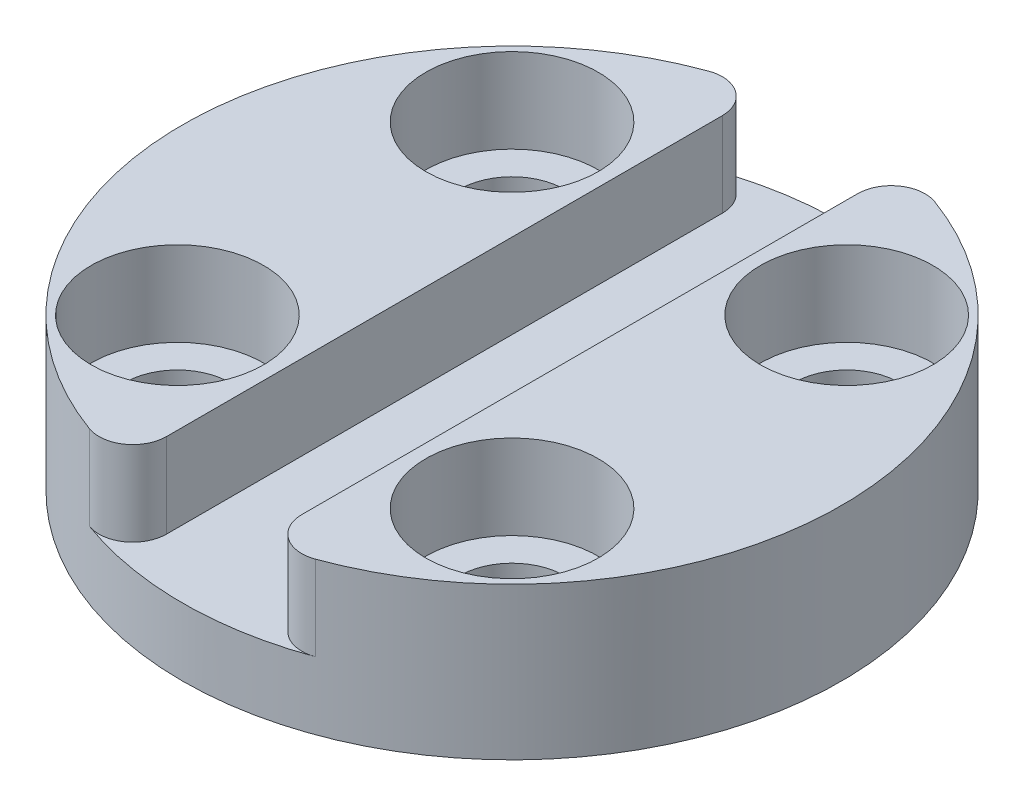
SolidWorks part; units mm, degrees
material "ABS"
ref_plane "前视基准面" through (0, 0, 0) normal (0, 0, 1) x (1, 0, 0)
ref_plane "上视基准面" through (0, 0, 0) normal (0, 1, 0) x (1, 0, 0)
ref_plane "右视基准面" through (0, 0, 0) normal (1, 0, 0) x (0, 0, -1)
sketch "草图1" plane through (0, 0, 0) normal (0, 1, 0) x (1, 0, 0)
  line L0 (0, 0) -> (8.1353, 8.1353) construction
  line L1 (0, 0) -> (0, 3.9878) construction
  circle A0 centre (0, 0) radius 9.75
  circle A1 centre (4.9497, 4.9497) radius 1.55
  circle A2 centre (4.9497, -4.9497) radius 1.55
  circle A3 centre (-4.9497, -4.9497) radius 1.55
  circle A4 centre (-4.9497, 4.9497) radius 1.55
  point P18 (0, 0)
  dimension "D1" = 19.5
  dimension "D2" = 3.1
  dimension "D3" = 7
  dimension "D4" = 45
  dimension "D5" = 4
extrude "凸台-拉伸1" add sketch "草图1" along normal blind 2
sketch "草图2" plane through (0, 2, 0) normal (0, 1, 0) x (1, 0, 0)
  line L0 (-2, 8.2196) -> (-2, -8.2196)
  line L1 (0, 0) -> (0, 3.7493) construction
  line L2 (2, 8.2196) -> (2, -8.2196)
  circle A0 centre (0, 0) radius 9.75 construction
  arc A1 (-3.3429, 9.159) -> (-3.3429, -9.159) centre (0, 0) ccw
  arc A2 (3.3429, -9.159) -> (3.3429, 9.159) centre (0, 0) ccw
  arc A3 (2, -8.2196) -> (3.3429, -9.159) centre (3, -8.2196) ccw
  circle A4 centre (-4.9497, 4.9497) radius 2.55
  circle A5 centre (4.9497, 4.9497) radius 2.55
  circle A6 centre (-4.9497, -4.9497) radius 2.55
  circle A7 centre (4.9497, -4.9497) radius 2.55
  arc A8 (-2, -8.2196) -> (-3.3429, -9.159) centre (-3, -8.2196) cw
  arc A9 (2, 8.2196) -> (3.3429, 9.159) centre (3, 8.2196) cw
  arc A10 (-2, 8.2196) -> (-3.3429, 9.159) centre (-3, 8.2196) ccw
  point P22 (2, -9.5427)
  point P25 (-2, -9.5427)
  point P28 (2, 9.5427)
  point P31 (-2, 9.5427)
  dimension "D1" = 5.1
  dimension "D2" = 4
  dimension "D3" = 1
extrude "凸台-拉伸2" add sketch "草图2" along normal blind 2.5
